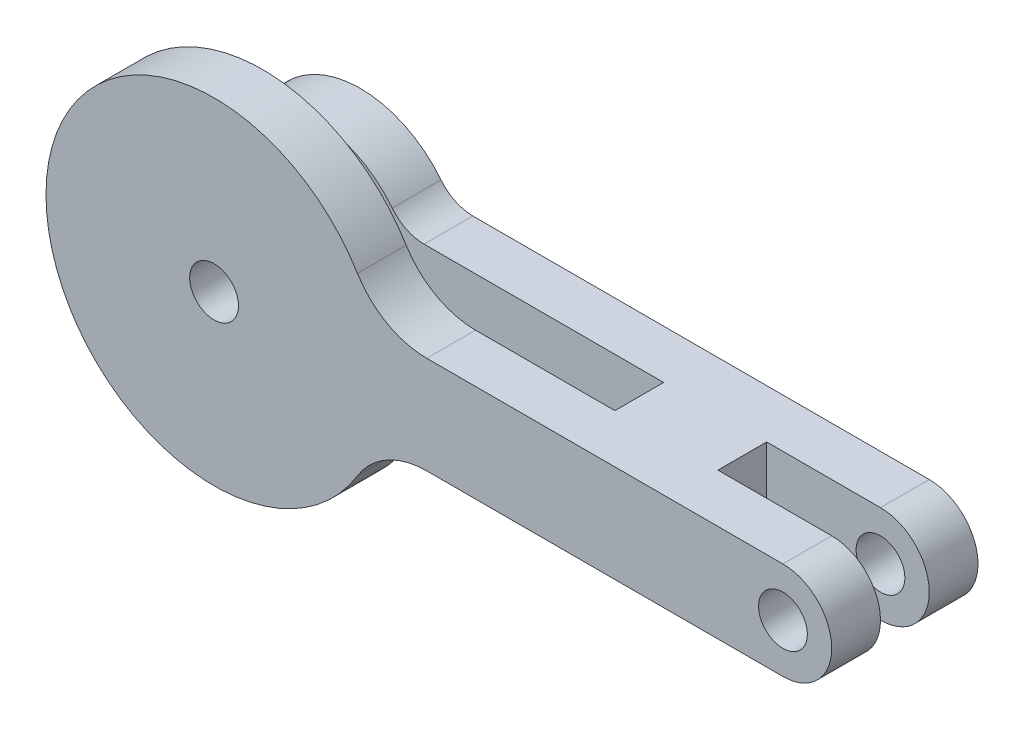
SolidWorks part; units mm, degrees
material "3.0205 (EN-AW 1200)"
ref_plane "Piano frontale" through (0, 0, 0) normal (0, 0, 1) x (1, 0, 0)
ref_plane "Piano superiore" through (0, 0, 0) normal (0, 1, 0) x (1, 0, 0)
ref_plane "Piano destro" through (0, 0, 0) normal (1, 0, 0) x (0, 0, -1)
sketch "Schizzo1" plane through (0, 0, 0) normal (0, 0, 1) x (1, 0, 0)
  line L0 (0, 0) -> (35, 0) construction
  line L2 (0, 3) -> (35, 3)
  line L3 (0, -3) -> (35, -3)
  circle A0 centre (0, 0) radius 10.34
  arc A1 (0, 3) -> (0, -3) centre (0, 0) ccw
  arc A2 (35, -3) -> (35, 3) centre (35, 0) ccw
  circle A3 centre (35, 0) radius 1.5
  circle A4 centre (0, 0) radius 1.5
  point P6 (17.5, 0)
  dimension "D1" = 20.68
  dimension "D2" = 3
  dimension "D3" = 3
  dimension "D4" = 35
  dimension "D5" = 6
extrude "Estrusione-Estrusione1" add sketch "Schizzo1" along normal blind 4.5 and the other way blind 4.5 contours L3 A2 L2 A0 A3 | A4 A0 L2 A1 L3 | A1 L2 A0 L3 region at (-3.2893, 0, 0) region at (4.3054, 0, 0) region at (23.274, 0, 0)
sketch "Schizzo2" plane through (0, -3, 0) normal (0, -1, 0) x (-1, 0, 0)
  line L0 (-38, -1.5) -> (10.34, -1.5) construction
  line L1 (-38, 4.5) -> (-38, -4.5) construction
  line L2 (10.34, -4.5) -> (10.34, 4.5) construction
  line L3 (-38, 1.5) -> (10.34, 1.5) construction
  line L4 (-38, -4.5) -> (-35, -4.5) construction
  line L5 (-9.8952, 4.5) -> (-35, 4.5) construction
  line L6 (10.34, -1.5) -> (-21.66, -1.5)
  line L7 (-21.66, -1.5) -> (-21.66, 1.5)
  line L8 (-21.66, 1.5) -> (10.34, 1.5)
  line L9 (10.34, 1.5) -> (10.34, -1.5)
  line L10 (-28, -1.5) -> (-38, -1.5)
  line L11 (-38, -1.5) -> (-38, 1.5)
  line L12 (-38, 1.5) -> (-28, 1.5)
  line L13 (-28, 1.5) -> (-28, -1.5)
  dimension "D1" = 3
  dimension "D2" = 3
  dimension "D3" = 32
  dimension "D4" = 10
extrude "Taglio-Estrusione1" cut sketch "Schizzo2" against normal blind 23.2843 and the other way blind 12.2777
sketch "Schizzo14" plane through (0, 0, -4.5) normal (0, 0, -1) x (-1, 0, 0)
  arc A0 (-9.8952, 3) -> (-7.8072, -6.7796) centre (0, 0) cw
  arc A1 (-9.8952, -3) -> (-9.8952, 3) centre (0, 0) ccw construction
  dimension "D1" = 10
sketch "Schizzo18" plane through (0, 0, -4.5) normal (0, 0, -1) x (-1, 0, 0)
  line L0 (-9.8952, 3) -> (-5.5853, 3)
  line L1 (-9.8952, -3) -> (-5.5853, -3)
  arc A1 (-9.8952, 3) -> (-9.8952, -3) centre (0, 0) cw
  arc A2 (-7.8072, -6.7796) -> (-9.8952, 3) centre (0, 0) ccw construction
  arc A3 (-5.5853, 3) -> (-5.5853, -3) centre (0, 0) cw
  dimension "D1" = 4
extrude "Taglio-Estrusione3" cut sketch "Schizzo18" against normal blind 3.5 contours L1 A3 L0 A1
fillet "Raccordo1" radius 5 1 edges at (9.8952, 3, 3)
fillet "Raccordo2" radius 5 1 edges at (9.8952, -3, 3)
fillet "Raccordo3" radius 2.5 1 edges at (5.5853, 3, -3)
fillet "Raccordo4" radius 2.5 1 edges at (5.5853, -3, -3)
